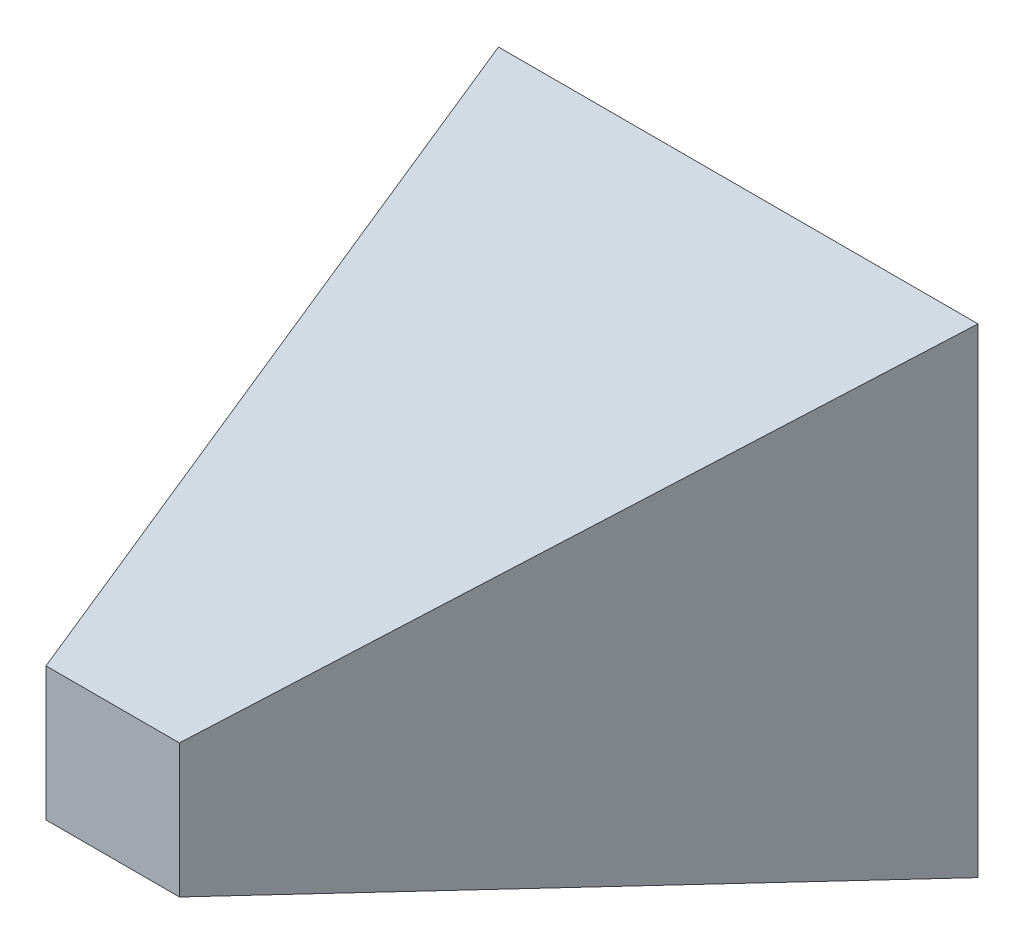
SolidWorks part; units mm, degrees
ref_plane "Front Plane" through (0, 0, 0) normal (0, 0, 1) x (1, 0, 0)
ref_plane "Top Plane" through (0, 0, 0) normal (0, 1, 0) x (1, 0, 0)
ref_plane "Right Plane" through (0, 0, 0) normal (1, 0, 0) x (0, 0, -1)
sketch "Sketch1" plane through (0, 0, 0) normal (0, 0, 1) x (1, 0, 0)
  line L1 (0, 0) -> (115, 0)
  line L2 (0, 0) -> (0, 115)
  line L3 (0, 115) -> (115, 115)
  line L4 (115, 0) -> (115, 115)
  dimension "D1" = 115
  dimension "D2" = 115
ref_plane "Plane1" through (0, 0, 150) normal (0, 0, 1) x (1, 0, 0)
sketch "Sketch2" plane through (0, 0, 150) normal (0, 0, 1) x (1, 0, 0)
  line L0 (57.5, 115) -> (57.5, 0) construction
  line L1 (41.5, 50.2216) -> (73.5, 50.2216)
  line L2 (41.5, 50.2216) -> (41.5, 82.2216)
  line L3 (41.5, 82.2216) -> (73.5, 82.2216)
  line L4 (73.5, 50.2216) -> (73.5, 82.2216)
  line L5 (0, 115) -> (115, 115) construction
  line L6 (0, 0) -> (115, 0) construction
  point P10 (0, 0)
  dimension "D1" = 32
  dimension "D2" = 32
loft "Loft1" add profiles "Sketch2", "Sketch1" connector at (41.5, 50.2216, 150) connector at (0, 0, 0)
